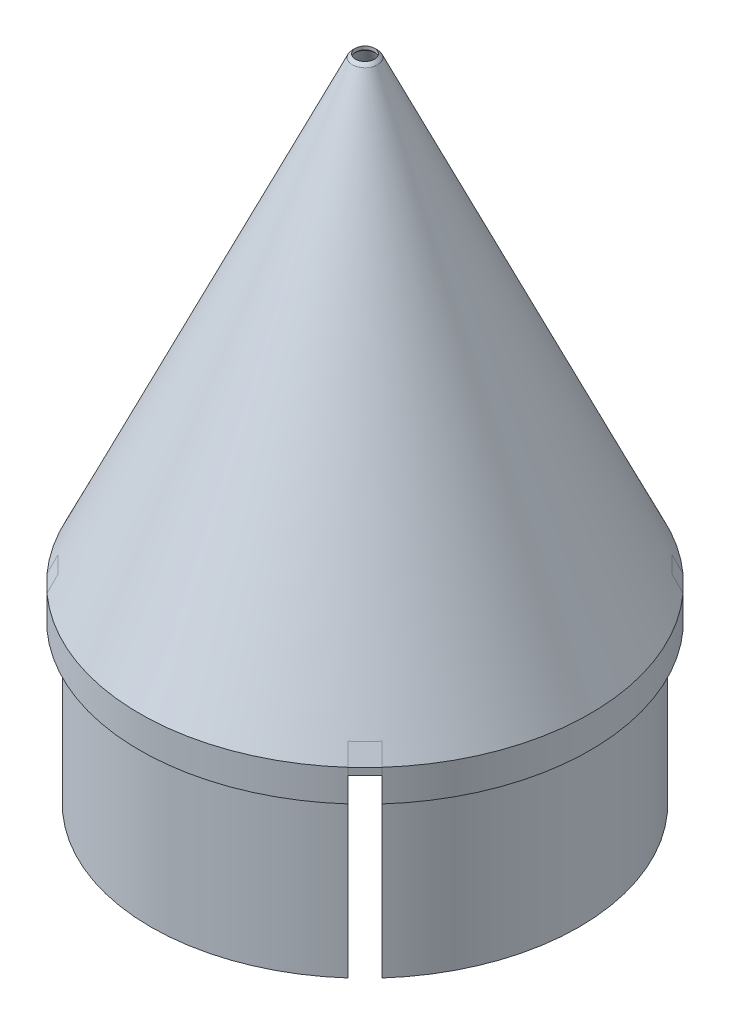
SolidWorks part; units mm, degrees
ref_plane "Front Plane" through (0, 0, 0) normal (0, 0, 1) x (1, 0, 0)
ref_plane "Top Plane" through (0, 0, 0) normal (0, 1, 0) x (1, 0, 0)
ref_plane "Right Plane" through (0, 0, 0) normal (1, 0, 0) x (0, 0, -1)
sketch "Sketch3" plane through (0, 0, 0) normal (0, 0, 1) x (1, 0, 0)
  line L1 (0, 0) -> (0, 155.682)
  line L4 (0, 0) -> (0, -50)
  line L5 (0, -50) -> (67.5, -50)
  line L6 (67.5, -50) -> (67.5, 0)
  line L9 (71, 0) -> (71, 10)
  line L11 (67.5, 0) -> (71, 0)
  line L12 (4, 153.682) -> (71, 10)
  line L13 (0, 229.1763) -> (0, 65.794) construction
  arc A0 (0, 155.682) -> (4, 153.682) centre (0, 150.682) cw
  point P11 (67.5, -50)
  point P14 (71, 10)
  dimension "Round yDim" = 2
  dimension "Lip Height" = 10
  dimension "Shoulder Height" = 50
  dimension "Half Angle" = 25
  dimension "Shoulder Diam" = 135
  dimension "Outer Diam" = 142
  dimension "Round xDim" = 8
revolve "Revolve1" add sketch "Sketch3" angle 360 about L1
shell "Shell1" thickness 0.8 removed face at (0, -50, -67.5)
sketch "Sketch7" plane through (0, 0, 0) normal (0, 1, 0) x (1, 0, 0)
  circle A0 centre (0, 0) radius 3
  dimension "PitotHoleDiam" = 6
extrude "Cut-Extrude3" cut sketch "Sketch7" along normal through all
ref_plane "Plane1" through (0, 0, 0) normal (1, 0, 0) x (0, 0, -1)
sketch "Sketch8" plane through (0, 0, 0) normal (1, 0, 0) x (0, 0, -1)
  line L0 (-39.807, 40.9099) -> (-39.807, 20) construction
  line L1 (-44.807, 44.0901) -> (-44.807, 39.0901) construction
  line L2 (-44.807, 39.0901) -> (-39.807, 40.9099) construction
  line L3 (-39.807, 40.9099) -> (-39.807, 35.9099)
  line L4 (-44.807, 44.0901) -> (-44.807, 39.0901)
  line L5 (-44.807, 39.0901) -> (-39.807, 40.9099)
  line L6 (-39.807, 35.9099) -> (-44.807, 34.0901)
  line L7 (-44.807, 34.0901) -> (-58.8839, 34.0901)
  line L8 (-3.3116, 153.2652) -> (-70.2, 9.8226) construction
  line L9 (-58.8839, 34.0901) -> (-44.807, 64.2781)
  line L10 (-44.807, 64.2781) -> (-44.807, 44.0901)
  dimension "D1" = 5
extrude "Boss-Extrude1" add sketch "Sketch8" along normal mid plane 15
sketch "Sketch9" plane through (0, 0, 0) normal (1, 0, 0) x (0, 0, -1)
  line L0 (-44.807, 39.0901) -> (-44.807, 62.9414) construction
  line L1 (-39.807, 40.9099) -> (-44.807, 39.0901) construction
  line L2 (-39.807, 35.9099) -> (-39.807, 40.9099) construction
  line L3 (-44.807, 34.0901) -> (-39.807, 35.9099) construction
  line L5 (-44.807, 39.0901) -> (-44.807, 62.9414)
  line L6 (-39.807, 40.9099) -> (-44.807, 39.0901)
  line L7 (-39.807, 35.9099) -> (-39.807, 40.9099)
  line L8 (-44.807, 34.0901) -> (-39.807, 35.9099)
  line L9 (-58.8839, 34.0901) -> (-44.807, 34.0901)
  line L10 (-44.807, 34.0901) -> (-44.807, 39.0901) construction
  line L11 (-44.807, 62.9414) -> (-58.8839, 34.0901)
  point P3 (0, 0)
  point P5 (-54.4202, 28.5399)
  point P7 (-61.3779, 24.5229)
  point P9 (-59.3233, 30.6654)
extrude "Cut-Extrude4" cut sketch "Sketch9" against normal mid plane 3.5
pattern_circular "CirPattern1" count 2 over 360 about axis through (0, 0, 0) along (0, -1, 0) of "Boss-Extrude1", "Cut-Extrude4"
ref_axis "Axis1" through (0, 0, 0) along (0, -1, 0)
ref_plane "Plane2" through (0, 0, 0) normal (0.7071, 0, 0.7071) x (0, -1, 0)
sketch "Sketch11" plane through (0, 0, 0) normal (0.7071, 0, 0.7071) x (0, -1, 0)
  line L0 (-12.58, 59.0623) -> (-16.4367, 63.6586) construction
  line L1 (-16.4367, 63.6586) -> (-1.1158, 76.5143) construction
  line L2 (-1.1158, 76.5143) -> (2.7409, 71.9181) construction
  line L3 (2.7409, 71.9181) -> (-12.58, 59.0623) construction
  line L4 (-14.5083, 61.3604) -> (0.8126, 74.2162) construction
  line L5 (-8.0805, 66.7) -> (-0.8, 66.7) construction
  line L6 (-15.3609, 53.7) -> (-15.3609, 67.3869)
  line L7 (-15.3609, 67.3869) -> (-9.8226, 70.2)
  line L8 (-8.0805, 53.7) -> (-13.9678, 65.2905) construction
  line L9 (-13.9678, 65.2905) -> (-15.0999, 67.5194) construction
  line L10 (-9.8226, 70.2) -> (-153.9335, -3) construction
  line L11 (-9.8226, 70.2) -> (-0.8, 70.2)
  line L15 (0, 0) -> (50, 0) construction
  line L16 (-0.8, 53.7) -> (-0.8, 66.7)
  line L17 (-0.8, 66.7) -> (-0.8, 70.2)
  circle A2 centre (-8.0805, 53.7) radius 13 construction
  circle A3 centre (-8.0805, 53.7) radius 10 construction
  arc A4 (-15.3609, 53.7) -> (-0.8, 53.7) centre (-8.0805, 53.7) ccw
  point P6 (-14.5083, 61.3604)
  dimension "Arm Wheel Diam Mock" = 20
  dimension "D4" = 2.5
  dimension "Arm Wheel Arm Width Mock" = 6
  dimension "Arm Wheel Arm Length Mock" = 20
  dimension "ArmAngle" = 40
extrude "Boss-Extrude3" add sketch "Sketch11" along normal mid plane 20
sketch "Sketch13" plane through (0, -50, 0) normal (0, -1, 0) x (1, 0, 0)
  line L0 (39.8946, -25.7525) -> (25.7525, -39.8946) construction
  line L1 (30.1719, -35.4752) -> (35.4752, -30.1719)
  line L2 (30.1719, -35.4752) -> (47.4829, -52.7862)
  line L3 (35.4752, -30.1719) -> (52.7862, -47.4829)
  arc A0 (47.4829, -52.7862) -> (52.7862, -47.4829) centre (0, 0) ccw
  circle A1 centre (0, 0) radius 71 construction
  point P11 (32.8236, -32.8236)
  point P12 (32.8236, -32.8236)
  dimension "ArmCutoutWidth" = 7.5
extrude "Cut-Extrude8" cut sketch "Sketch13" against normal up to surface (65.3609 mm away) up to face at (44.3114, 15.3609, -44.3114)
hole_wizard "M4 Clearance Hole1" positions "Sketch14" profile "Sketch15" hole size "M4" standard "ANSI Metric"
sketch "Sketch14" plane through (7.0711, 0, 7.0711) normal (0.7071, 0, 0.7071) x (0.7071, 0, -0.7071)
  arc A0 (53.7, 15.3609) -> (53.7, 0.8) centre (53.7, 8.0805) ccw construction
  point P0 (53.7, 8.0805)
sketch "Sketch15" plane through (45.0427, 8.0805, -30.9006) normal (0, 1, 0) x (0.7071, 0, -0.7071)
  line L0 (0, 0) -> (0, 21.4421)
  line L1 (0, 21.4421) -> (2.4, 20)
  line L2 (2.4, 20) -> (2.4, 0)
  line L5 (2.4, 0) -> (0, 0)
  line L10 (0, 21.4421) -> (-2.4, 20) construction
  line L11 (0, -6.35) -> (0, 107.95) construction
  dimension "Hole Dia." = 4.8
  dimension "Hole Depth" = 20
  dimension "Drill Angle" = 118
sketch "Sketch17" plane through (0, 0, 0) normal (0.7071, 0, 0.7071) x (0, -1, 0)
  line L0 (-15.3609, 67.6175) -> (-153.2652, 3.3116) construction
  line L1 (-48.9892, 51.9363) -> (-47.1766, 52.7816)
  line L8 (-48.9892, 51.9363) -> (-48.0732, 49.972)
  line L9 (-47.1766, 52.7816) -> (-46.2606, 50.8172)
  arc A0 (-48.0732, 49.972) -> (-46.2606, 50.8172) centre (-47.1669, 50.3946) ccw
  circle A1 centre (-47.1669, 50.3946) radius 0.25
  point P11 (-153.1459, 3.4703)
  dimension "D1" = 1
  dimension "D2" = 0.5
extrude "Boss-Extrude4" add sketch "Sketch17" along normal mid plane 2.5
pattern_circular "CirPattern4" count 4 over 360 about axis through (0, 0, 0) along (0, -1, 0) of "M4 Clearance Hole1", "Boss-Extrude3", "Boss-Extrude4", "Cut-Extrude8"
sketch "Sketch18" plane through (1.9445, 0, -7.2478) normal (0.7071, 0, 0.7071) x (0.7071, 0, -0.7071)
  line L0 (61.8974, 15.3609) -> (64.4009, 10)
  line L1 (64.4009, 10) -> (64.4009, 7.8056)
  line L2 (64.4009, 10) -> (64.4009, 0) construction
  line L3 (64.4009, 7.8056) -> (62.5843, 9.9705)
  line L6 (61.0134, 15.3609) -> (61.8974, 15.3609)
  line L7 (62.5843, 9.9705) -> (62.5843, 5.3699) construction
  circle A1 centre (47.2, 8.0805) radius 15 construction
  circle A3 centre (47.2, 8.0805) radius 2.4 construction
  arc A4 (58.8643, 16.7375) -> (57.751, 18.0643) centre (57.9246, 17.0795) ccw construction
  arc A6 (62.5843, 9.9705) -> (61.0134, 15.3609) centre (52.5508, 9.9705) ccw
  point P10 (64.4256, 5.5546)
  point P12 (62.0239, 8.0805)
  point P18 (62.3678, 10.2285)
  dimension "D1" = 15
  dimension "D2" = 13
  dimension "ArmStopperAngle" = 40
  dimension "D4" = 15.5
extrude "Boss-Extrude6" add sketch "Sketch18" along normal up to next
pattern_circular "CirPattern8" count 4 over 360 about axis through (0, 0, 0) along (0, -1, 0) of "Boss-Extrude6"
equation "\"LegAngle\"=30"
